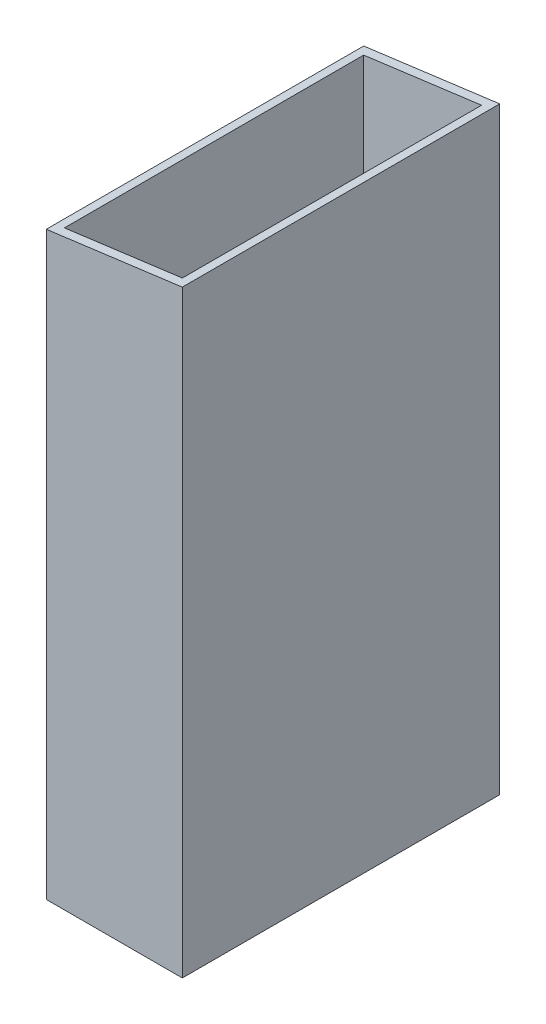
SolidWorks part; units mm, degrees
ref_plane "前视基准面" through (0, 0, 0) normal (0, 0, 1) x (1, 0, 0)
ref_plane "上视基准面" through (0, 0, 0) normal (0, 1, 0) x (1, 0, 0)
ref_plane "右视基准面" through (0, 0, 0) normal (1, 0, 0) x (0, 0, -1)
other "Configuration Table"
sketch "草图1" plane through (0, 0, 0) normal (0, 0, 1) x (1, 0, 0)
  line L1 (15, -375) -> (-15, -375)
  line L2 (15, -375) -> (15, 375)
  line L3 (15, 375) -> (-15, 375)
  line L4 (-15, -375) -> (-15, 375)
  line L5 (15, -375) -> (-15, 375) construction
  line L6 (15, 375) -> (-15, -375) construction
  point P0 (0, 0)
  dimension "D1" = 30
  dimension "D2" = 750
extrude "凸台-拉伸2" add sketch "草图1" along normal blind 70
sketch "草图2" plane through (0, -375, 0) normal (0, -1, 0) x (1, 0, 0)
  line L0 (-15, 70) -> (-15, 0) construction
  line L1 (-13, 68) -> (13, 68)
  line L2 (-13, 68) -> (-13, 2)
  line L3 (-13, 2) -> (13, 2)
  line L4 (13, 68) -> (13, 2)
  line L5 (-13, 68) -> (13, 2) construction
  line L6 (-13, 2) -> (13, 68) construction
  line L7 (-15, 70) -> (15, 70) construction
  line L8 (15, 70) -> (15, 0) construction
  line L9 (-15, 0) -> (15, 0) construction
  point P0 (0, 35)
  dimension "D1" = 2
  dimension "D2" = 2
  dimension "D3" = 2
  dimension "D4" = 2
extrude "切除-拉伸3" cut sketch "草图2" against normal through all contours L2 L1 L4 L3
sketch "草图3" plane through (0, 0, 70) normal (0, 0, 1) x (1, 0, 0)
  line L0 (15, 375) -> (-15, 371.0504)
  line L1 (-15, 375) -> (-15, -375) construction
  line L2 (15, -375) -> (15, 375) construction
  line L3 (15, -347.1) -> (-15, -343.1504)
  line L4 (-15, -343.1504) -> (-15, -376.6872)
  line L5 (-15, -376.6872) -> (15, -376.6872)
  line L6 (15, -376.6872) -> (15, -347.1)
  line L7 (-15, 371.0504) -> (-15, 377.0408)
  line L8 (-15, 377.0408) -> (15, 377.0408)
  line L9 (15, 377.0408) -> (15, 375)
  line M2 (-15, 375) -> (-15, -375)
  line M3 (-15, -375) -> (15, -375)
  line M4 (15, -375) -> (15, 375)
  dimension "D1" = 82.5
  dimension "D2" = 82.5
  dimension "D3" = 722.1
extrude "切除-拉伸4" cut sketch "草图3" against normal through all contours L3 M4 M2 M3 | L9 L0 L7 L8 region at (-0.3305, -360.0408, 70)
sketch "草图4" plane through (0, 0, 0) normal (0, 0, -1) x (-1, 0, 0)
  line L0 (-15, 243.0504) -> (15, 243.0504)
  line L1 (-15, -347.1) -> (-15, 375) construction
  line L2 (15, 371.0504) -> (15, -343.1504) construction
  line L3 (-15, 243.0504) -> (-15, -679.8701)
  line L4 (-15, -679.8701) -> (15, -679.8701)
  line L5 (15, -679.8701) -> (15, 243.0504)
  point P6 (0, 0)
  dimension "D1" = 128
extrude "切除-拉伸5" cut sketch "草图4" against normal through all
